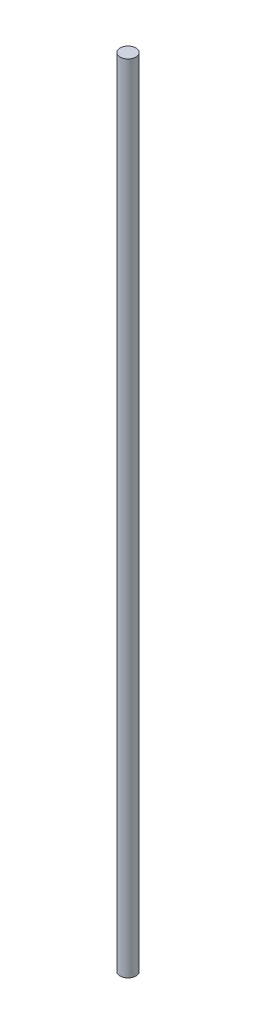
SolidWorks part; units mm, degrees
ref_plane "前基準面" through (0, 0, 0) normal (0, 0, 1) x (1, 0, 0)
ref_plane "上基準面" through (0, 0, 0) normal (0, 1, 0) x (1, 0, 0)
ref_plane "右基準面" through (0, 0, 0) normal (1, 0, 0) x (0, 0, -1)
sketch "草圖1" plane through (0, 0, 0) normal (0, 1, 0) x (1, 0, 0)
  circle A0 centre (0, 0) radius 4
  dimension "D1" = 8
extrude "填料-伸長1" add sketch "草圖1" along normal blind 400
